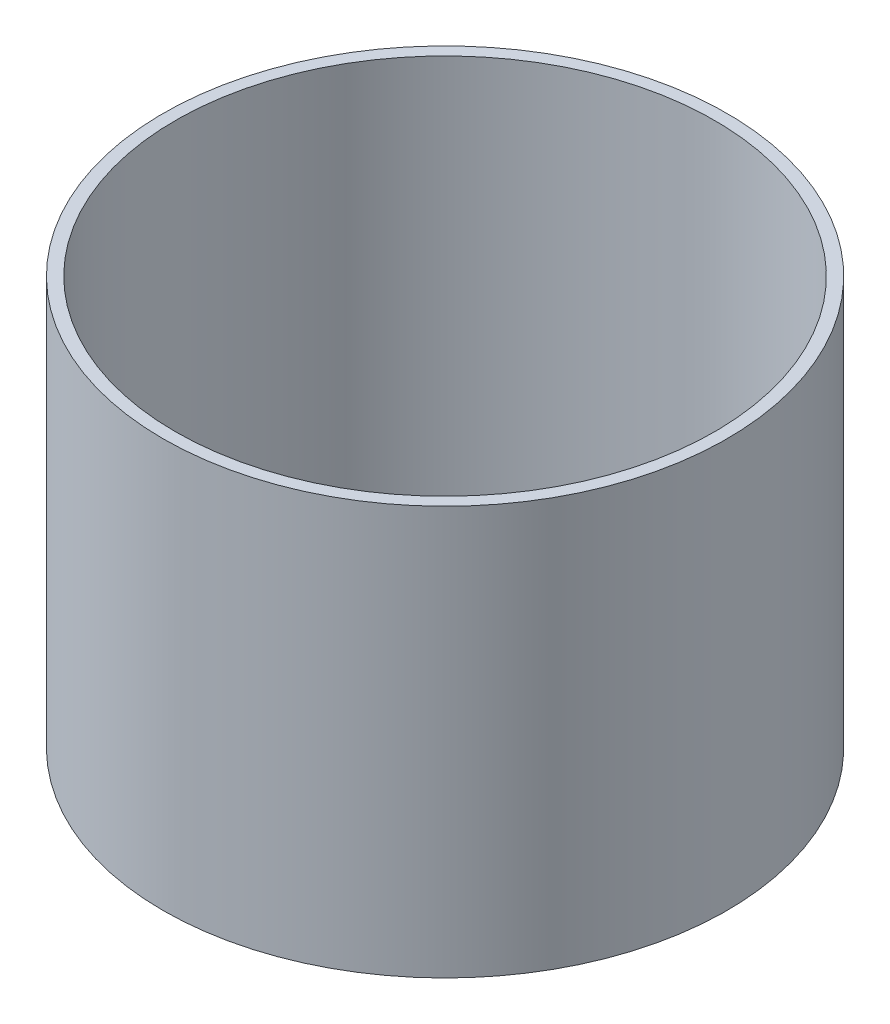
SolidWorks part; units mm, degrees
ref_plane "Front Plane" through (0, 0, 0) normal (0, 0, 1) x (1, 0, 0)
ref_plane "Top Plane" through (0, 0, 0) normal (0, 1, 0) x (1, 0, 0)
ref_plane "Right Plane" through (0, 0, 0) normal (1, 0, 0) x (0, 0, -1)
sketch "Sketch1" plane through (0, 0, 0) normal (0, 1, 0) x (1, 0, 0)
  circle A0 centre (0, 0) radius 69
  circle A1 centre (0, 0) radius 66
  dimension "D1" = 138
  dimension "D2" = 3
extrude "Boss-Extrude1" add sketch "Sketch1" along normal blind 100
sketch "Sketch2" plane through (0, 0, 0) normal (0, 1, 0) x (1, 0, 0)
  line L0 (0, 0) -> (-101.9987, 0) construction
  line L1 (0, 0) -> (-86.7855, -58.5376) construction
  line L2 (-62.1778, -41.9395) -> (-81.9858, -12.573) construction
  dimension "D1" = 34
  dimension "D2" = 75
ref_plane "Plane1" through (-62.1778, 0, 41.9395) normal (0.829, 0, -0.5592) x (-0.5592, 0, -0.829)
sketch "Sketch3" plane through (-62.1778, 0, 41.9395) normal (0.829, 0, -0.5592) x (-0.5592, 0, -0.829)
  line L0 (10, 38.5) -> (10, 66.5)
  line L1 (10, 66.5) -> (-10, 66.5)
  line L2 (-10, 66.5) -> (-10, 38.5)
  line L3 (-10, 38.5) -> (10, 38.5)
  point P2 (0, 38.5)
  dimension "D1" = 20
  dimension "D2" = 38.5
  dimension "D3" = 28
  dimension "D4" = 0
extrude "Cut-Extrude1" cut sketch "Sketch3" along normal up to next
fillet "Fillet1" radius 3 4 edges at (-49.7503, 38.5, 45.6192) (-60.9341, 38.5, 29.0384) (-49.7503, 66.5, 45.6192) (-60.9341, 66.5, 29.0384)
